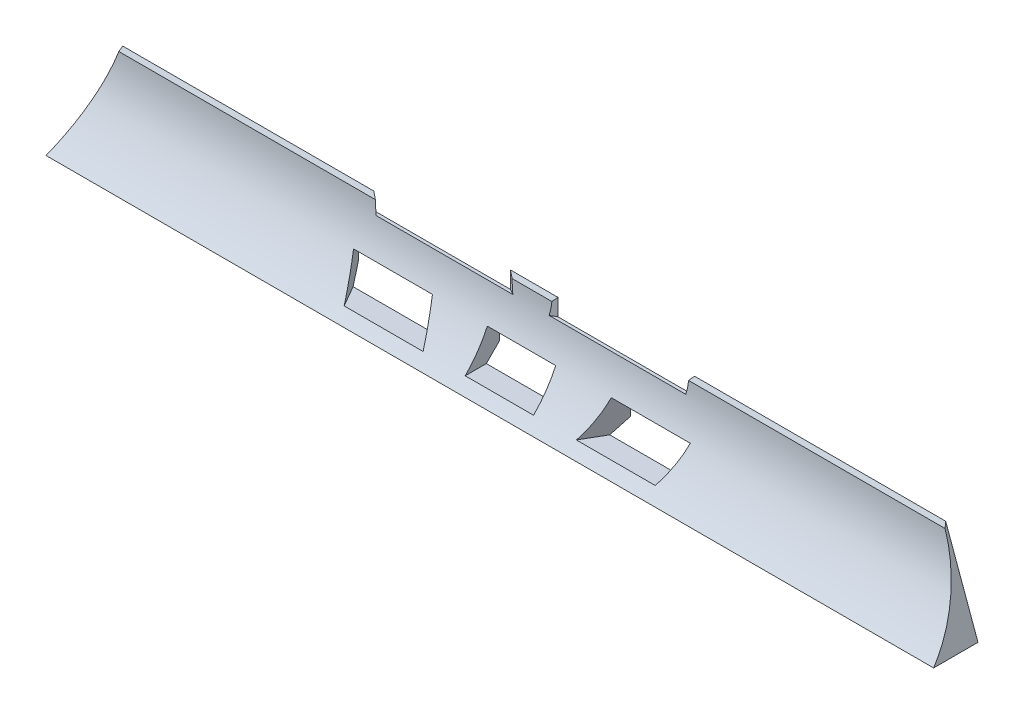
SolidWorks part; units mm, degrees
ref_plane "Front Plane" through (0, 0, 0) normal (0, 0, 1) x (1, 0, 0)
ref_plane "Top Plane" through (0, 0, 0) normal (0, 1, 0) x (1, 0, 0)
ref_plane "Right Plane" through (0, 0, 0) normal (1, 0, 0) x (0, 0, -1)
sketch "Sketch1" plane through (0, 0, 0) normal (1, 0, 0) x (0, 0, -1)
  line L0 (0, 0) -> (-10, 0)
  line L1 (-10, 0) -> (0, 20)
  line L2 (0, 20) -> (0, 0)
  dimension "D1" = 10
  dimension "D2" = 20
extrude "Boss-Extrude1" add sketch "Sketch1" along normal blind 200
sketch "Sketch2" plane through (200, 0, 0) normal (1, 0, 0) x (0, 0, -1)
  line L0 (0, 20) -> (-10, 0) construction
  line L1 (-10, 0) -> (0, 0) construction
  line L2 (0, 0) -> (0, 20) construction
  line L3 (-10, 0) -> (-0.5, 19)
  arc A0 (-10, 0) -> (-0.5, 19) centre (-25.4923, 19.6211) ccw
  dimension "D3" = 25
  dimension "D1" = 0
  dimension "D2" = 0.5
extrude "Cut-Extrude1" cut sketch "Sketch2" against normal through all
sketch "Sketch4" plane through (200, 0, 0) normal (1, 0, 0) x (0, 0, -1)
  line L0 (-5, 0) -> (0, 5)
  line L1 (-10, 0) -> (0, 0) construction
  line L2 (0, 0) -> (0, 20) construction
  line L3 (0, 5) -> (0, 0)
  line L4 (0, 0) -> (-5, 0)
  dimension "D1" = 5
  dimension "D2" = 5
extrude "Cut-Extrude2" cut sketch "Sketch4" against normal through all
sketch "Sketch5" plane through (0, 0, 0) normal (0, 0, -1) x (-1, 0, 0)
  line L0 (0, 0) -> (-200, 0) construction
  line L1 (-200, 5) -> (-197, 5)
  line L2 (-200, 5) -> (-200, 0)
  line L3 (-200, 0) -> (-197, 0)
  line L4 (-197, 5) -> (-197, 0)
  dimension "D1" = 3
extrude "Boss-Extrude2" add sketch "Sketch5" against normal up to surface up to face at (100, 2.5, 2.5)
ref_plane "Plane1" through (100, 0, 0) normal (1, 0, 0) x (0, 0, -1)
sketch "Sketch6" plane through (0, 0, 0) normal (0, 0, -1) x (-1, 0, 0)
  line L0 (-200, 20) -> (-192.7206, 20)
  line L1 (-200, 20) -> (0, 20) construction
  line L2 (-192.7206, 20) -> (-200, 0)
  line L3 (-200, 20) -> (-200, 0)
  dimension "D1" = 20
extrude "Cut-Extrude3" cut sketch "Sketch6" against normal through all
mirror "Mirror2" about plane through (100, 0, 0) normal (1, 0, 0) of "Cut-Extrude3", "Boss-Extrude2"
sketch "Sketch7" plane through (0, 0, 0) normal (0, 0, -1) x (-1, 0, 0)
  line L1 (-159.8316, 11) -> (-167.8316, 11)
  line L2 (-159.8316, 11) -> (-159.8316, 0)
  line L3 (-159.8316, 0) -> (-167.8316, 0)
  line L4 (-167.8316, 11) -> (-167.8316, 0)
  line L5 (-160.8316, 11) -> (-166.8316, 11) construction
  line L6 (-166.8316, 0) -> (-160.8316, 0) construction
  line L7 (-166.8316, 11) -> (-166.8316, 0) construction
  dimension "D1" = 8
  dimension "D2" = 1
extrude "Boss-Extrude3" add sketch "Sketch7" against normal up to next
sketch "Sketch8" plane through (0, 0, 0) normal (0, 0, -1) x (-1, 0, 0)
  line L1 (-165.5637, 8.5) -> (-167.2957, 5.5)
  line L2 (-167.2957, 5.5) -> (-165.5637, 2.5)
  line L3 (-165.5637, 2.5) -> (-162.0995, 2.5)
  line L4 (-162.0995, 2.5) -> (-160.3675, 5.5)
  line L5 (-160.3675, 5.5) -> (-162.0995, 8.5)
  line L6 (-162.0995, 8.5) -> (-165.5637, 8.5)
  line L7 (-167.8316, 0) -> (-159.8316, 0) construction
  line L8 (-165.3316, 8) -> (-165.3316, 3) construction
  circle A2 centre (-163.8316, 5.5) radius 3 construction
  point P1 (-163.4276, 5.5)
  point P10 (0, 0)
  point P13 (-163.8316, 8.5)
  dimension "D1" = 6
  dimension "D2" = 1.5
  dimension "D3" = 5.5
extrude "Cut-Extrude4" cut sketch "Sketch8" against normal blind 1.8 contours L5 L6 L1 L2 L3 L4 | L1 L2 L3 L4 L5 L6 region at (163.8316, 5.5, 0)
mirror "Mirror3" about plane through (100, 0, 0) normal (1, 0, 0) of "Cut-Extrude4", "Boss-Extrude3"
sketch "Sketch9" plane through (0, 0, 0) normal (0, 0, 1) x (1, 0, 0)
  line L1 (92.2158, 2) -> (107.6158, 2)
  line L2 (92.2158, 2) -> (92.2158, 9.2)
  line L3 (92.2158, 9.2) -> (107.6158, 9.2)
  line L4 (107.6158, 2) -> (107.6158, 9.2)
extrude "Cut-Extrude6" cut sketch "Sketch9" along normal through all
ref_plane "Plane2" through (32.136, 0, -55.6612) normal (-0.5, 0, 0.866) x (0.866, 0, 0.5)
sketch "Sketch10" plane through (32.136, 0, -55.6612) normal (-0.5, 0, 0.866) x (0.866, 0, 0.5)
  line L1 (105.439, 2) -> (120.839, 2)
  line L2 (105.439, 2) -> (105.439, 9.2)
  line L3 (105.439, 9.2) -> (120.839, 9.2)
  line L4 (120.839, 2) -> (120.839, 9.2)
  point P4 (0, 0)
  point P7 (0, 0)
extrude "Cut-Extrude8" cut sketch "Sketch10" along normal blind 15.8 and the other way blind 6.8
ref_plane "Plane3" through (115.6697, 0, -66.7819) normal (-0.866, 0, 0.5) x (0.5, 0, 0.866)
sketch "Sketch11" plane through (115.6697, 0, -66.7819) normal (-0.866, 0, 0.5) x (0.5, 0, 0.866)
  line L1 (68.0717, 25) -> (52.6717, 25)
  line L2 (68.0717, 25) -> (68.0717, 16.2)
  line L3 (68.0717, 16.2) -> (52.6717, 16.2)
  line L4 (52.6717, 25) -> (52.6717, 16.2)
  line L7 (52.6717, 25) -> (52.6717, 17.8) construction
  line L8 (47.1217, 16.2) -> (73.6217, 16.2) construction
  point P5 (0, 0)
extrude "Cut-Extrude9" cut sketch "Sketch11" along normal blind 97.8
mirror "Mirror4" about plane through (100, 0, 0) normal (1, 0, 0) of "Cut-Extrude8", "Cut-Extrude9"
